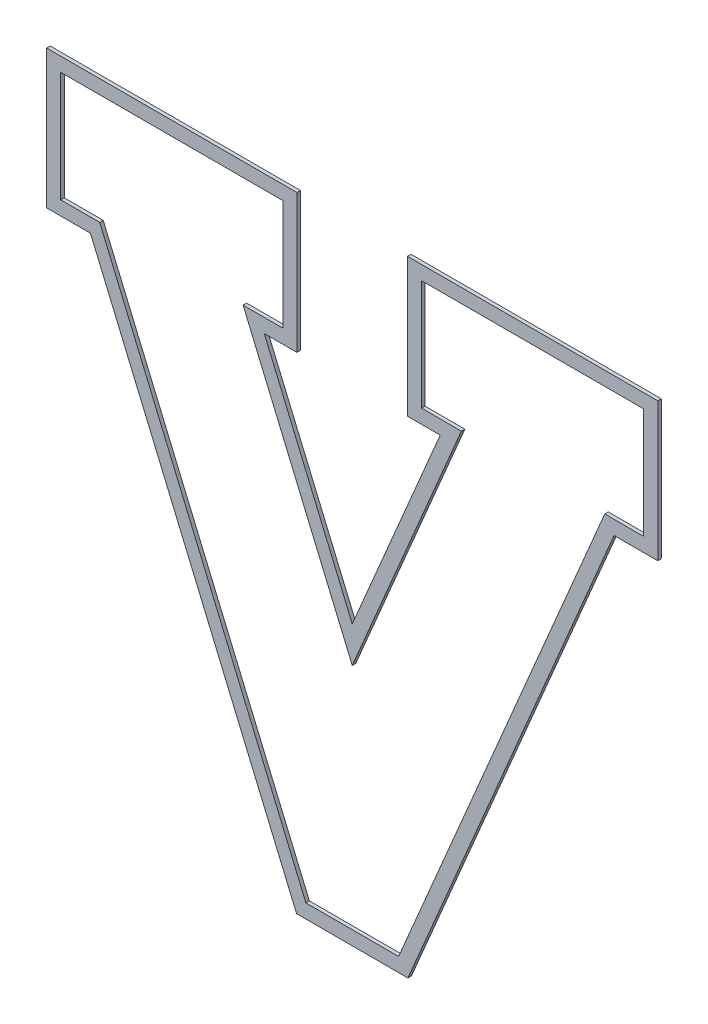
SolidWorks part; units mm, degrees
material "6061 Alloy"
ref_plane "Front Plane" through (0, 0, 0) normal (0, 0, 1) x (1, 0, 0)
ref_plane "Top Plane" through (0, 0, 0) normal (0, 1, 0) x (1, 0, 0)
ref_plane "Right Plane" through (0, 0, 0) normal (1, 0, 0) x (0, 0, -1)
sketch "Sketch1" plane through (0, 0, 0) normal (0, 0, 1) x (1, 0, 0)
  line B0 (326.5754, 440.106) -> (356.1251, 440.106)
  line B1 (356.1251, 440.106) -> (276.5171, 252.3248)
  line B2 (276.5171, 252.3248) -> (196.9092, 440.106)
  line B3 (196.9092, 440.106) -> (226.4589, 440.106)
  line B4 (226.4589, 440.106) -> (226.4589, 565.4544)
  line B5 (226.4589, 565.4544) -> (0, 565.4544)
  line B6 (0, 565.4544) -> (0, 440.106)
  line B7 (0, 440.106) -> (39.5592, 440.106)
  line B8 (39.5592, 440.106) -> (226.1378, 0)
  line B9 (226.1378, 0) -> (326.8965, 0)
  line B10 (326.8965, 0) -> (513.4751, 440.106)
  line B11 (513.4751, 440.106) -> (553.0343, 440.106)
  line B12 (553.0343, 440.106) -> (553.0343, 565.4544)
  line B13 (553.0343, 565.4544) -> (326.5754, 565.4544)
  line B14 (326.5754, 565.4544) -> (326.5754, 440.106)
  line B15 (318.4864, 12.7) -> (234.5479, 12.7)
  line B16 (505.065, 452.806) -> (318.4864, 12.7)
  line B17 (540.3343, 452.806) -> (505.065, 452.806)
  line B18 (540.3343, 552.7544) -> (540.3343, 452.806)
  line B19 (339.2754, 552.7544) -> (540.3343, 552.7544)
  line B20 (339.2754, 452.806) -> (339.2754, 552.7544)
  line B21 (375.3033, 452.806) -> (339.2754, 452.806)
  line B22 (276.5171, 219.7869) -> (375.3033, 452.806)
  line B23 (177.731, 452.806) -> (276.5171, 219.7869)
  line B24 (213.7589, 452.806) -> (177.731, 452.806)
  line B25 (213.7589, 552.7544) -> (213.7589, 452.806)
  line B26 (12.7, 552.7544) -> (213.7589, 552.7544)
  line B27 (12.7, 452.806) -> (12.7, 552.7544)
  line B28 (47.9692, 452.806) -> (12.7, 452.806)
  line B29 (234.5479, 12.7) -> (47.9692, 452.806)
sketch_block_instance "V_Block-1"
sketch_block "V_Block"
extrude "Boss-Extrude1" add sketch "Sketch1" along normal blind 3.175
